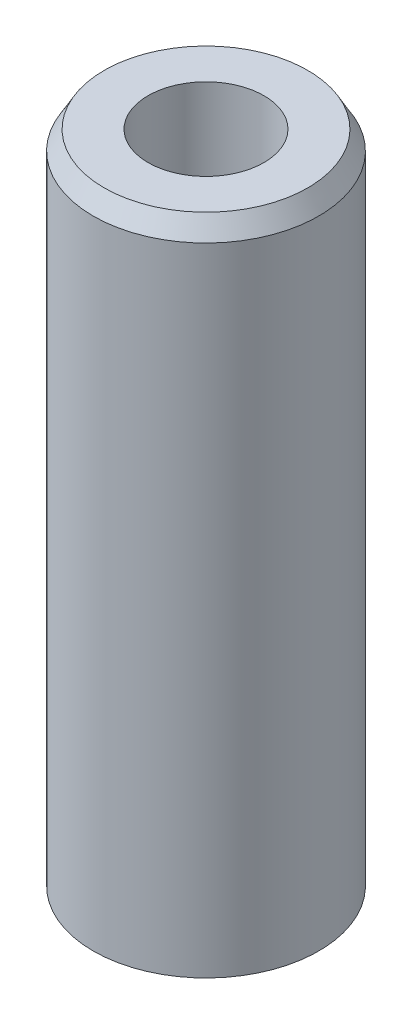
SolidWorks part; units mm, degrees
ref_plane "Front Plane" through (0, 0, 0) normal (0, 0, 1) x (1, 0, 0)
ref_plane "Top Plane" through (0, 0, 0) normal (0, 1, 0) x (1, 0, 0)
ref_plane "Right Plane" through (0, 0, 0) normal (1, 0, 0) x (0, 0, -1)
sketch "Sketch1" plane through (0, 0, 0) normal (0, 1, 0) x (1, 0, 0)
  circle A0 centre (0, 0) radius 10
  dimension "SHAFT_OD" = 20
extrude "Boss-Extrude1" add sketch "Sketch1" along normal blind 59.1041
sketch "Sketch2" plane through (0, 0, 0) normal (0, 1, 0) x (1, 0, 0)
  circle A0 centre (0, 0) radius 5.1434
  dimension "BORE_D" = 10.2867
extrude "Cut-Extrude1" cut sketch "Sketch2" along normal through all
chamfer "Chamfer1" distance 1.6813 angle 30 2 edges at (0, 59.1041, 10) (0, 0, 10) first distance on face at (0, 59.1041, 10) first distance on face at (0, 0, 5.1434)
